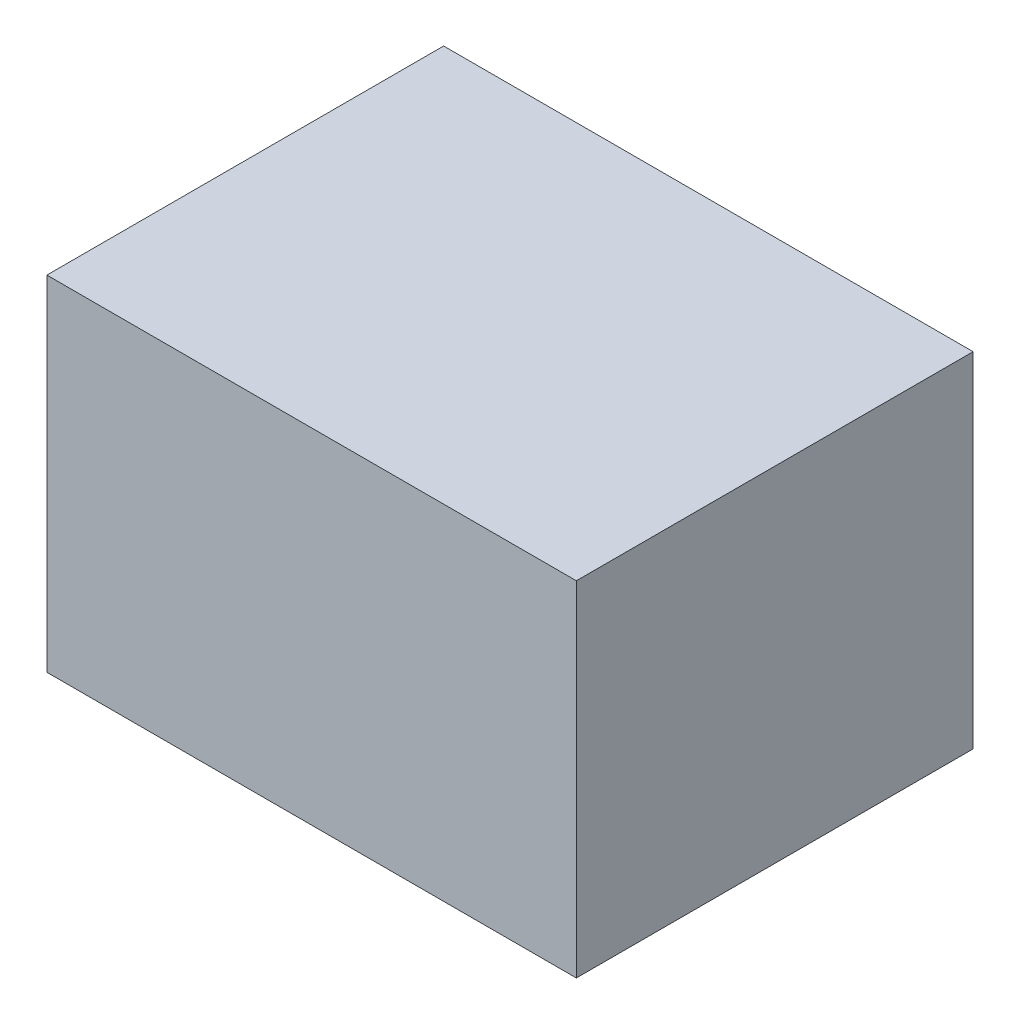
SolidWorks part; units mm, degrees
ref_plane "Front Plane" through (0, 0, 0) normal (0, 0, 1) x (1, 0, 0)
ref_plane "Top Plane" through (0, 0, 0) normal (0, 1, 0) x (1, 0, 0)
ref_plane "Right Plane" through (0, 0, 0) normal (1, 0, 0) x (0, 0, -1)
sketch "Sketch2" plane through (0, 0, 0) normal (0, 0, 1) x (1, 0, 0)
  line L1 (1562.1, 1016) -> (-14.0301, 1016)
  line L2 (1562.1, 1016) -> (1562.1, -8.078)
  line L3 (1562.1, -8.078) -> (-14.0301, -8.078)
  line L4 (-14.0301, 1016) -> (-14.0301, -8.078)
  point P4 (0, 0)
extrude "Boss-Extrude1" add sketch "Sketch2" along normal blind 1181.1 contours L1 L4 L3 L2
move or copy body "Body-Move/Copy1" bodies to move or copy 101 copy no translate (-1570.5895, 0, 0) parameters "D1"=1570.5895, "D2"=0, "D3"=0
